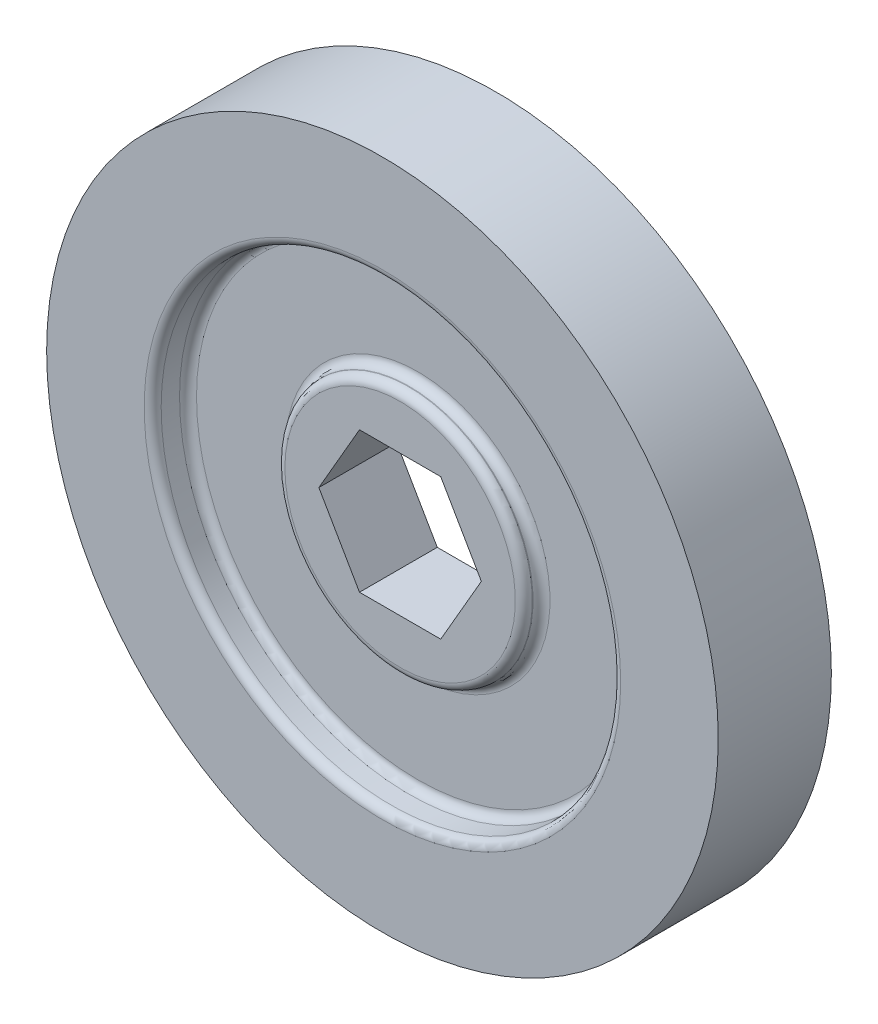
SolidWorks part; units mm, degrees
ref_plane "Front Plane" through (0, 0, 0) normal (0, 0, 1) x (1, 0, 0)
ref_plane "Top Plane" through (0, 0, 0) normal (0, 1, 0) x (1, 0, 0)
ref_plane "Right Plane" through (0, 0, 0) normal (1, 0, 0) x (0, 0, -1)
sketch "Sketch1" plane through (0, 0, 0) normal (0, 0, 1) x (1, 0, 0)
  circle A0 centre (0, 0) radius 30.1625
  dimension "D1" = 60.325
extrude "Boss-Extrude1" add sketch "Sketch1" along normal blind 5.08 and the other way blind 5.08
sketch "Sketch2" plane through (0, 0, 5.08) normal (0, 0, 1) x (1, 0, 0)
  line L1 (3.6489, 6.32) -> (-3.6489, 6.32)
  line L2 (-3.6489, 6.32) -> (-7.2977, 0)
  line L3 (-7.2977, 0) -> (-3.6489, -6.32)
  line L4 (-3.6489, -6.32) -> (3.6489, -6.32)
  line L5 (3.6489, -6.32) -> (7.2977, 0)
  line L6 (7.2977, 0) -> (3.6489, 6.32)
  circle A0 centre (0, 0) radius 6.32 construction
  dimension "D1" = 12.64
extrude "Cut-Extrude1" cut sketch "Sketch2" against normal through all
sketch "Sketch3" plane through (0, 0, 0) normal (1, 0, 0) x (0, 0, -1)
  line L0 (3.4925, 11.1125) -> (1.905, 11.1125)
  line L1 (5.08, -30.1625) -> (5.08, 30.1625) construction
  line L2 (1.905, 11.1125) -> (1.905, 20.6375)
  line L3 (1.905, 20.6375) -> (5.08, 20.6375)
  line L4 (5.08, 20.6375) -> (5.08, 0)
  line L5 (22.753, 0) -> (-27.7028, 0) construction
  line L6 (5.08, 30.1625) -> (-5.08, 30.1625) construction
  line L7 (5.08, 0) -> (3.4925, 0)
  line L8 (3.4925, 0) -> (3.4925, 11.1125)
  dimension "D1" = 9.525
  dimension "D2" = 9.525
  dimension "D3" = 1.5875
  dimension "D4" = 3.175
revolve "Cut-Revolve1" cut sketch "Sketch3" angle 360 about L5
fillet "Fillet1" radius 0.762 3 edges at (-11.1125, 0, -1.905) (-20.6375, 0, -5.08) (-11.1125, 0, -3.4925)
mirror "Mirror1" about plane through (0, 0, 0) normal (0, 0, 1) of "Cut-Revolve1"
fillet "Fillet2" radius 0.762 4 edges at (-20.6375, 0, 5.08) (-20.6375, 0, 1.905) (-11.1125, 0, 1.905) (-11.1125, 0, 3.4925)
